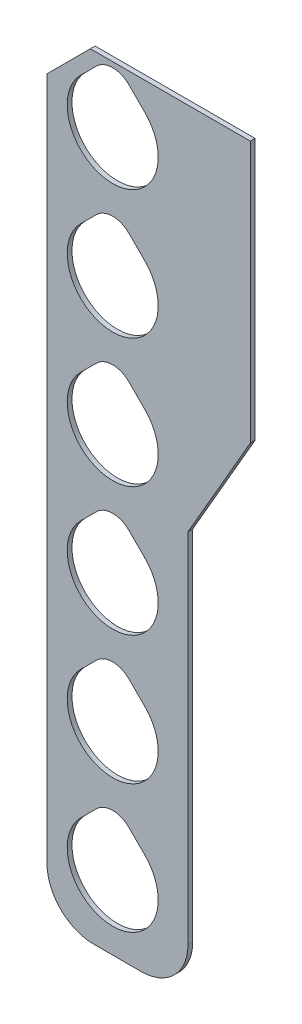
SolidWorks part; units mm, degrees
ref_plane "前视基准面" through (0, 0, 0) normal (0, 0, 1) x (1, 0, 0)
ref_plane "上视基准面" through (0, 0, 0) normal (0, 1, 0) x (1, 0, 0)
ref_plane "右视基准面" through (0, 0, 0) normal (1, 0, 0) x (0, 0, -1)
sketch "草图1" plane through (0, 0, 0) normal (0, 0, 1) x (1, 0, 0)
  line L0 (-3.3411, 10.0232) -> (-6.6822, 6.6822) construction
  line L1 (6.6822, 6.6822) -> (3.3411, 10.0232) construction
  line L2 (29.0767, 92.6495) -> (29.0767, 147.8038) construction
  line L3 (29.0767, 147.8038) -> (-4.7766, 147.8038) construction
  line L4 (-4.7766, 147.8038) -> (-14, 138.5805) construction
  line L5 (-14, 138.5805) -> (-14, -5) construction
  line L6 (-4, -15) -> (6, -15) construction
  line L7 (16, -5) -> (16, 70) construction
  line L8 (16, 70) -> (29.0767, 92.6495) construction
  line L9 (-3.3411, 37.0232) -> (-6.6822, 33.6822) construction
  line L10 (6.6822, 33.6822) -> (3.3411, 37.0232) construction
  line L11 (6.6822, 60.6822) -> (3.3411, 64.0232) construction
  line L12 (-3.3411, 64.0232) -> (-6.6822, 60.6822) construction
  line L13 (-3.3411, 91.0232) -> (-6.6822, 87.6822) construction
  line L21 (6.6822, 87.6822) -> (3.3411, 91.0232) construction
  line L22 (6.6822, 141.6822) -> (3.3411, 145.0232) construction
  line L23 (-3.3411, 145.0232) -> (-6.6822, 141.6822) construction
  line L24 (-3.3411, 118.0232) -> (-6.6822, 114.6822) construction
  line L25 (6.6822, 114.6822) -> (3.3411, 118.0232) construction
  line L26 (26.3284, 101.5038) -> (24.0767, 105.4038) construction
  line L27 (21.825, 101.5038) -> (26.3284, 101.5038) construction
  line L28 (24.0767, 105.4038) -> (21.825, 101.5038) construction
  line L29 (21.825, 131.5038) -> (26.3284, 131.5038) construction
  line L30 (24.0767, 135.4038) -> (21.825, 131.5038) construction
  line L31 (26.3284, 131.5038) -> (24.0767, 135.4038) construction
  line L32 (28.8767, 92.7031) -> (28.8767, 147.6038)
  line L33 (28.8767, 147.6038) -> (-4.6938, 147.6038)
  line L34 (-4.6938, 147.6038) -> (-13.8, 138.4976)
  line L35 (-13.8, 138.4976) -> (-13.8, -5)
  line L36 (-4, -14.8) -> (6, -14.8)
  line L37 (15.8, -5) -> (15.8, 70.0536)
  line L38 (15.8, 70.0536) -> (28.8767, 92.7031)
  line L39 (-3.4118, 10.0939) -> (-6.7529, 6.7529)
  line L40 (6.7529, 6.7529) -> (3.4118, 10.0939)
  line L41 (6.7529, 33.7529) -> (3.4118, 37.0939)
  line L42 (-3.4118, 37.0939) -> (-6.7529, 33.7529)
  line L43 (6.7529, 60.7529) -> (3.4118, 64.0939)
  line L44 (-3.4118, 64.0939) -> (-6.7529, 60.7529)
  line L45 (-3.4118, 91.0939) -> (-6.7529, 87.7529)
  line L46 (6.7529, 87.7529) -> (3.4118, 91.0939)
  line L47 (-3.4118, 118.0939) -> (-6.7529, 114.7529)
  line L48 (6.7529, 114.7529) -> (3.4118, 118.0939)
  line L49 (6.7529, 141.7529) -> (3.4118, 145.0939)
  line L50 (-3.4118, 145.0939) -> (-6.7529, 141.7529)
  line L51 (26.5016, 101.4038) -> (24.0767, 105.6038)
  line L52 (24.0767, 105.6038) -> (21.6518, 101.4038)
  line L53 (21.6518, 101.4038) -> (26.5016, 101.4038)
  line L54 (21.6518, 131.4038) -> (26.5016, 131.4038)
  line L55 (26.5016, 131.4038) -> (24.0767, 135.6038)
  line L56 (24.0767, 135.6038) -> (21.6518, 131.4038)
  arc A0 (-14, -5) -> (-4, -15) centre (-4, -5) ccw construction
  arc A1 (6, -15) -> (16, -5) centre (6, -5) ccw construction
  arc A2 (-6.6822, 6.6822) -> (6.6822, 6.6822) centre (0, 0) ccw construction
  arc A3 (3.3411, 10.0232) -> (-3.3411, 10.0232) centre (0, 6.6822) ccw construction
  arc A6 (3.3411, 37.0232) -> (-3.3411, 37.0232) centre (0, 33.6822) ccw construction
  arc A7 (-6.6822, 33.6822) -> (6.6822, 33.6822) centre (0, 27) ccw construction
  arc A8 (-6.6822, 60.6822) -> (6.6822, 60.6822) centre (0, 54) ccw construction
  arc A9 (3.3411, 64.0232) -> (-3.3411, 64.0232) centre (0, 60.6822) ccw construction
  arc A10 (3.3411, 91.0232) -> (-3.3411, 91.0232) centre (0, 87.6822) ccw construction
  arc A11 (-6.6822, 87.6822) -> (6.6822, 87.6822) centre (0, 81) ccw construction
  arc A12 (3.3411, 145.0232) -> (-3.3411, 145.0232) centre (0, 141.6822) ccw construction
  arc A13 (-6.6822, 141.6822) -> (6.6822, 141.6822) centre (0, 135) ccw construction
  arc A14 (3.3411, 118.0232) -> (-3.3411, 118.0232) centre (0, 114.6822) ccw construction
  arc A15 (-6.6822, 114.6822) -> (6.6822, 114.6822) centre (0, 108) ccw construction
  arc A16 (-13.8, -5) -> (-4, -14.8) centre (-4, -5) ccw
  arc A17 (6, -14.8) -> (15.8, -5) centre (6, -5) ccw
  arc A18 (-6.7529, 6.7529) -> (6.7529, 6.7529) centre (0, 0) ccw
  arc A19 (3.4118, 10.0939) -> (-3.4118, 10.0939) centre (0, 6.6822) ccw
  arc A20 (-6.7529, 33.7529) -> (6.7529, 33.7529) centre (0, 27) ccw
  arc A21 (3.4118, 37.0939) -> (-3.4118, 37.0939) centre (0, 33.6822) ccw
  arc A22 (3.4118, 64.0939) -> (-3.4118, 64.0939) centre (0, 60.6822) ccw
  arc A23 (-6.7529, 60.7529) -> (6.7529, 60.7529) centre (0, 54) ccw
  arc A24 (-6.7529, 87.7529) -> (6.7529, 87.7529) centre (0, 81) ccw
  arc A25 (3.4118, 91.0939) -> (-3.4118, 91.0939) centre (0, 87.6822) ccw
  arc A26 (-6.7529, 114.7529) -> (6.7529, 114.7529) centre (0, 108) ccw
  arc A27 (3.4118, 118.0939) -> (-3.4118, 118.0939) centre (0, 114.6822) ccw
  arc A28 (3.4118, 145.0939) -> (-3.4118, 145.0939) centre (0, 141.6822) ccw
  arc A29 (-6.7529, 141.7529) -> (6.7529, 141.7529) centre (0, 135) ccw
  dimension "D1" = 0.2
  dimension "D2" = 0.1
  dimension "D3" = 0.1
  dimension "D4" = 0.1
  dimension "D5" = 0.1
  dimension "D6" = 0.1
  dimension "D7" = 0.1
  dimension "D8" = 0.1
  dimension "D9" = 0.1
extrude "凸台-拉伸1" add sketch "草图1" along normal blind 1 contours L36 A17 L37 L38 L32 L33 L34 L35 A16 L31 L29 L30 L28 L26 L27 A3 L1 A2 L0 A7 L9 A6 L10 A9 L11 A8 L12 A11 L13 A10 L21 A13 L23 A12 L22 A15 L24 A14 L25 | L32 L33 L34 L35 A16 L36 A17 L37 L38 | L39 A18 L40 A19 | A20 L41 A21 L42 | L43 A22 L44 A23 | L45 A24 L46 A25 | L47 A26 L48 A27 | L49 A28 L50 A29 region at (20.8841, 82.2179, 0)
